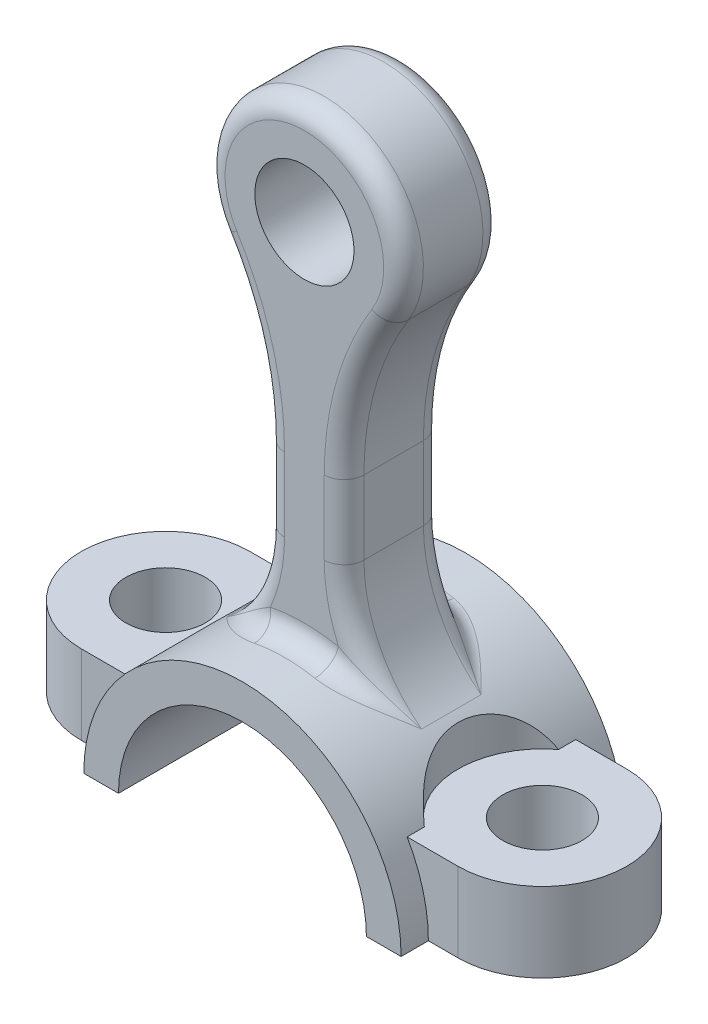
SolidWorks part; units mm, degrees
ref_plane "前视基准面" through (0, 0, 0) normal (0, 0, 1) x (1, 0, 0)
ref_plane "上视基准面" through (0, 0, 0) normal (0, 1, 0) x (1, 0, 0)
ref_plane "右视基准面" through (0, 0, 0) normal (1, 0, 0) x (0, 0, -1)
sketch "草图4" plane through (0, 0, 0) normal (0, 1, 0) x (1, 0, 0)
  line L0 (0, 12.1506) -> (0, -8.6135) construction
  circle A0 centre (-19, 0) radius 4
  circle A2 centre (-19, 0) radius 8.5
  circle A3 centre (19, 0) radius 4
  circle A4 centre (19, 0) radius 8.5
  dimension "D1" = 8
  dimension "D2" = 19
  dimension "D3" = 17
extrude "凸台-拉伸1" add sketch "草图4" along normal blind 8
sketch "草图5" plane through (0, 0, 0) normal (0, 0, 1) x (1, 0, 0)
  circle A0 centre (0, 0) radius 12.5
  dimension "D2" = 25
extrude "切除-拉伸1" cut sketch "草图5" against normal mid plane 20
sketch "草图6" plane through (0, 0, 0) normal (0, 0, 1) x (1, 0, 0)
  line L7 (-16, 0) -> (-12.5, 0)
  line L8 (12.5, 0) -> (16, 0)
  arc A3 (16, 0) -> (-16, 0) centre (0, 0) ccw
  arc A4 (12.5, 0) -> (-12.5, 0) centre (0, 0) ccw
  dimension "D1" = 32
extrude "凸台-拉伸3" add sketch "草图6" along normal mid plane 22.5
sketch "草图7" plane through (0, 8, 0) normal (0, 1, 0) x (1, 0, 0)
  circle A0 centre (-19, 0) radius 8.5
extrude "切除-拉伸2" cut sketch "草图7" along normal through all
sketch "草图8" plane through (0, 8, 0) normal (0, 1, 0) x (1, 0, 0)
  line L5 (-19, -8.5) -> (-19, -4)
  line L6 (-19, 4) -> (-19, 8.5)
  line L7 (-19, 8.5) -> (-13.4618, 8.5)
  line L8 (-13.4618, 8.5) -> (-13.4618, -8.5)
  line L9 (-13.4618, -8.5) -> (-19, -8.5)
  arc A3 (-19, -4) -> (-19, 4) centre (-19, 0) ccw
  arc A4 (-13.8564, 6.7671) -> (-13.8564, -6.7671) centre (-19, 0) ccw construction
extrude "凸台-拉伸4" add sketch "草图8" against normal up to surface (8 mm away) up to face at (-19.5, 0, 0)
sketch "草图9" plane through (0, 8, 0) normal (0, 1, 0) x (1, 0, 0)
  circle A0 centre (-19, 0) radius 4
extrude "切除-拉伸3" cut sketch "草图9" against normal through all
mirror "镜向1" about plane through (0, 0, 0) normal (1, 0, 0) of "切除-拉伸2", "凸台-拉伸4", "切除-拉伸3"
sketch "草图10" plane through (0, 0, 0) normal (0, 0, 1) x (1, 0, 0)
  line L0 (16, 0) -> (19, 0) construction
  line L1 (0, 0) -> (0, 40.7604) construction
  line L2 (-4, 31.9287) -> (-4, 24.4949)
  line L3 (4, 31.9287) -> (4, 24.4949)
  circle A0 centre (0, 53) radius 5
  arc A1 (8.5, 47.7322) -> (-8.5, 47.7322) centre (0, 53) ccw
  arc A2 (-9.8065, 12.6425) -> (-4, 24.4949) centre (-19, 24.4949) ccw
  arc A3 (16, 0) -> (-16, 0) centre (0, 0) ccw construction
  arc A4 (-4, 31.9287) -> (-8.5, 47.7322) centre (-34, 31.9287) ccw
  arc A5 (9.8065, 12.6425) -> (-9.8065, 12.6425) centre (0, 0) ccw
  arc A6 (4, 31.9287) -> (8.5, 47.7322) centre (34, 31.9287) cw
  arc A7 (9.8065, 12.6425) -> (4, 24.4949) centre (19, 24.4949) cw
  dimension "D1" = 20
  dimension "D2" = 10
  dimension "D4" = 30
  dimension "D5" = 60
  dimension "D3" = 53
  dimension "D6" = 4
extrude "凸台-拉伸5" add sketch "草图10" along normal mid plane 10
fillet "圆角1" radius 2 14 edges at (5.5296, 17.8958, 5) (4, 28.2118, 5) (5.1469, 40.1445, 5) (0, 63, 5) (-5.5296, 17.8958, 5) (-4, 28.2118, 5) (5.5296, 17.8958, -5) (4, 28.2118, -5) (5.1469, 40.1445, -5) (0, 63, -5) (-5.5296, 17.8958, -5) (-4, 28.2118, -5) (-5.1469, 40.1445, 5) (-5.1469, 40.1445, -5)
fillet "圆角2" radius 2 6 edges at (-6.4006, 14.664, -4.7209) (0, 16, -5) (-6.4006, 14.664, 4.7209) (0, 16, 5) (6.4006, 14.664, -4.7209) (6.4006, 14.664, 4.7209)
